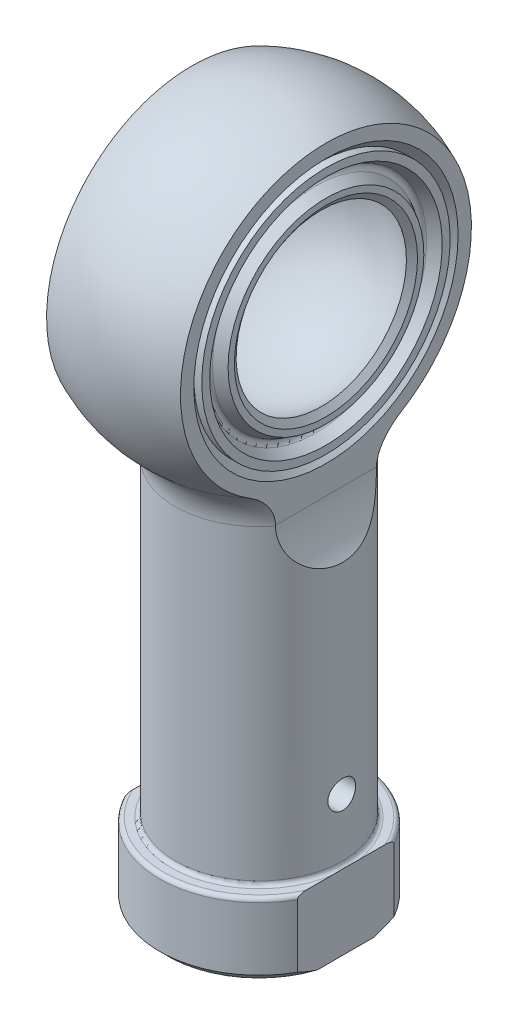
SolidWorks part; units mm, degrees
material "AISI 316 Annealed Stainless Steel Bar (SS)"
ref_plane "Front Plane" through (0, 0, 0) normal (0, 0, 1) x (1, 0, 0)
ref_plane "Top Plane" through (0, 0, 0) normal (0, 1, 0) x (1, 0, 0)
ref_plane "Right Plane" through (0, 0, 0) normal (1, 0, 0) x (0, 0, -1)
sketch "Sketch1" plane through (0, 0, 0) normal (0, 0, 1) x (1, 0, 0)
  line L0 (0, -1004.5939) -> (0, 0) construction
  line L1 (3.5719, 0) -> (6.35, 0)
  line L2 (6.35, 0) -> (6.35, 4.7752)
  line L3 (6.35, 4.7752) -> (5.3594, 4.7752)
  line L4 (5.3594, 4.7752) -> (5.3594, 26.204)
  line L5 (0, 34.925) -> (0, 45.1612)
  line L6 (3.5719, 0) -> (3.5719, 19.05)
  line L7 (3.5719, 19.05) -> (3.3179, 19.05)
  line L8 (3.3179, 19.05) -> (3.3179, 22.225)
  line L9 (3.3179, 22.225) -> (0.889, 23.6844)
  line L10 (0.889, 23.6844) -> (0.889, 34.036)
  line L11 (0.889, 34.036) -> (0, 34.925)
  arc A0 (0, 45.1612) -> (5.3594, 26.204) centre (0, 34.925) cw
  dimension "D" = 20.4724
  dimension "A" = 34.925
  dimension "E" = 10.7188
  dimension "K" = 12.7
  dimension "F" = 4.7752
  dimension "Thread" = 7.1437
  dimension "C" = 19.05
  dimension "D1" = 59
  dimension "D2" = 1.778
  dimension "P" = 22.225
  dimension "D3" = 0.254
  dimension "D4" = 45
revolve "Revolve1" add sketch "Sketch1" angle 360 about L0
chamfer "Chamfer1" distance 0.508 angle 45 1 edges at (0, 0, -6.35)
fillet "Fillet1" radius 3.048 1 edges at (0, 26.204, -5.3594)
fillet "Fillet2" radius 0.254 2 edges at (0, 4.7752, -6.35) (0, 4.7752, -5.3594)
sketch "Sketch2" plane through (0, 0, 0) normal (0, 0, 1) x (1, 0, 0)
  line L0 (-5.5499, 0) -> (5.5499, 0)
  line L1 (5.5499, 0) -> (5.5499, 21.3287)
  line L2 (-5.5499, 0) -> (-5.5499, 21.3287)
  line L3 (-4.2799, 45.1612) -> (4.2799, 45.1612)
  line L4 (4.2799, 45.1612) -> (4.2799, 24.6888)
  line L5 (-4.2799, 45.1612) -> (-4.2799, 24.6888)
  line L6 (-4.2799, 24.6888) -> (4.2799, 24.6888) construction
  arc A0 (-4.2799, 24.6888) -> (-5.5499, 21.3287) centre (-9.3599, 24.6888) cw
  arc A1 (4.2799, 24.6888) -> (5.5499, 21.3287) centre (9.3599, 24.6888) ccw
  arc A2 (6.4784, 26.9997) -> (-6.4784, 26.9997) centre (0, 34.925) ccw construction
  arc A3 (5.3594, 26.204) -> (0, 45.1612) centre (0, 34.925) ccw construction
  dimension "D1" = 5.08
  dimension "J" = 11.0998
  dimension "H" = 8.5598
extrude "Cut-Extrude1" cut sketch "Sketch2" against normal through all both and the other way through all flip side to cut
sketch "Sketch3" plane through (0, 0, 0) normal (1, 0, 0) x (0, 0, -1)
  circle A0 centre (0, 34.925) radius 7.9375
  arc A1 (0, 45.1612) -> (-6.4784, 26.9997) centre (0, 34.925) ccw construction
  circle A2 centre (0, 8.7186) radius 0.889
  dimension "D1" = 1.778
  dimension "S" = 15.875
  dimension "D2" = 8.7186
extrude "Cut-Extrude2" cut sketch "Sketch3" against normal through all both and the other way through all
sketch "Sketch4" plane through (0, 0, 0) normal (0, 0, 1) x (1, 0, 0)
  line L0 (-14.4492, 34.925) -> (16.2709, 34.925) construction
  line L1 (-4.2799, 34.925) -> (4.2799, 34.925) construction
  line L2 (3.9801, 40.3689) -> (4.2799, 40.779)
  line L3 (4.2799, 40.779) -> (4.2799, 41.1813)
  line L4 (4.2799, 42.8625) -> (-4.2799, 42.8625)
  line L5 (-4.2799, 42.8625) -> (-4.2799, 42.3545)
  line L6 (-4.2799, 40.779) -> (-3.9801, 40.3689)
  line L7 (4.2799, 42.8625) -> (-4.2799, 42.8625) construction
  line L8 (4.2799, 26.9997) -> (4.2799, 44.2235) construction
  line L9 (-4.2799, 44.2235) -> (-4.2799, 26.9997) construction
  line L10 (4.2799, 42.3545) -> (3.6449, 41.9879)
  line L11 (3.6449, 41.5479) -> (4.2799, 41.1813)
  line L12 (4.2799, 42.3545) -> (4.2799, 42.8625)
  line L13 (-4.2799, 42.3545) -> (-3.6449, 41.9879)
  line L14 (-3.6449, 41.5479) -> (-4.2799, 41.1813)
  line L15 (-4.2799, 41.1813) -> (-4.2799, 40.779)
  arc A0 (-3.9801, 40.3689) -> (3.9801, 40.3689) centre (0, 34.925) cw
  arc A1 (0, 45.1612) -> (-4.2799, 44.2235) centre (0, 34.925) ccw construction
  arc A2 (3.6449, 41.9879) -> (3.6449, 41.5479) centre (3.7719, 41.7679) ccw
  arc A3 (-3.6449, 41.9879) -> (-3.6449, 41.5479) centre (-3.7719, 41.7679) cw
  dimension "D1" = 0.508
  dimension "Ball_Dia" = 13.4874
  dimension "D2" = 0.254
  dimension "D3" = 0.508
  dimension "D4" = 0.762
  dimension "D5" = 60
revolve "Revolve2" add sketch "Sketch4" angle 360 about L0
chamfer "Chamfer2" distance 0.508 angle 45 2 edges at (-4.2799, 26.9875, 0) (4.2799, 42.8625, 0)
equation "\"D2@Sketch3\"=\"Thread@Sketch1\"+.062"
